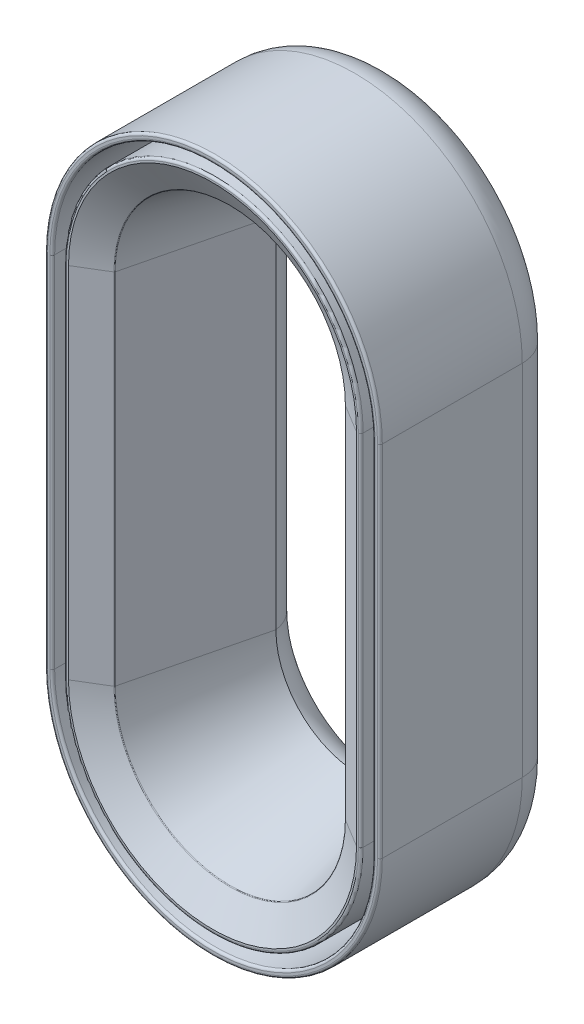
SolidWorks part; units mm, degrees
ref_plane "Ön Düzlem" through (0, 0, 0) normal (0, 0, 1) x (1, 0, 0)
ref_plane "Üst Düzlem" through (0, 0, 0) normal (0, 1, 0) x (1, 0, 0)
ref_plane "Sağ Düzlem" through (0, 0, 0) normal (1, 0, 0) x (0, 0, -1)
sketch "Çizim1" plane through (0, 0, 0) normal (0, 0, 1) x (1, 0, 0)
  line L0 (0, -150) -> (0, 150) construction
  line L1 (-140, -150) -> (-140, 150)
  line L2 (140, -150) -> (140, 150)
  arc A0 (-140, -150) -> (140, -150) centre (0, -150) ccw
  arc A1 (140, 150) -> (-140, 150) centre (0, 150) ccw
  point P2 (0, 0)
  dimension "D1" = 140
  dimension "D2" = 300
extrude "Yükseklik-Ekstrüzyon1" add sketch "Çizim1" along normal blind 150
sketch "Çizim2" plane through (0, 0, 150) normal (0, 0, 1) x (1, 0, 0)
  line L0 (0, -150) -> (0, 150) construction
  line L1 (-70, -150) -> (-70, 150)
  line L2 (70, -150) -> (70, 150)
  arc A0 (-70, -150) -> (70, -150) centre (0, -150) ccw
  arc A1 (70, 150) -> (-70, 150) centre (0, 150) ccw
  point P2 (0, 0)
  dimension "D2" = 70
  dimension "D1" = 300
extrude "Kes-Ekstrüzyon1" cut sketch "Çizim2" against normal blind 150
chamfer "Pah1" distance 30 distance2 123 4 edges at (-70, 0, 150) (0, -220, 150) (0, 220, 150) (70, 0, 150) first distance on face at (0, 0, 150)
sketch "Çizim3" plane through (0, 0, 150) normal (0, 0, 1) x (1, 0, 0)
  line L0 (140, -150) -> (140, 150) construction
  line L1 (-140, 150) -> (-140, -150) construction
  line L2 (140, -150) -> (140, 150)
  line L3 (-140, 150) -> (-140, -150)
  line L4 (-134, 150) -> (-134, -150)
  line L5 (134, -150) -> (134, 150)
  line L6 (-124, 150) -> (-124, -150)
  line L7 (124, -150) -> (124, 150)
  arc A0 (-140, -150) -> (140, -150) centre (0, -150) ccw construction
  arc A1 (140, 150) -> (-140, 150) centre (0, 150) ccw construction
  arc A2 (-140, -150) -> (140, -150) centre (0, -150) ccw
  arc A3 (140, 150) -> (-140, 150) centre (0, 150) ccw
  arc A4 (134, 150) -> (-134, 150) centre (0, 150) ccw
  arc A5 (-134, -150) -> (134, -150) centre (0, -150) ccw
  arc A6 (124, 150) -> (-124, 150) centre (0, 150) ccw
  arc A7 (-124, -150) -> (124, -150) centre (0, -150) ccw
  dimension "D1" = 6
  dimension "D2" = 10
extrude "Kes-Ekstrüzyon2" cut sketch "Çizim3" against normal blind 76 contours L4 A5 L5 A4 A7 L6 A6 L7 region at (0, 277.7195, 150)
sketch "Çizim4" plane through (0, 0, 0) normal (0, 1, 0) x (1, 0, 0)
  line L0 (0, 0) -> (0, -150)
  line L1 (-140, -150) -> (140, -150) construction
  circle A0 centre (0, -75) radius 3.7566
extrude "Kes-Ekstrüzyon3" cut sketch "Çizim4" against normal blind 10 from offset 287 contours L0 A0 | L0 A0 region at (1.5944, 0, 75) region at (-1.5944, 0, 75) offset against normal yes
fillet "Radyus1" radius 31 8 edges at (0, -220, 0) (-70, 0, 0) (0, 220, 0) (0, 290, 0) (140, 0, 0) (0, -290, 0) (70, 0, 0) (-140, 0, 0)
fillet "Radyus2" radius 2 12 edges at (-140, 0, 150) (0, 290, 150) (140, 0, 150) (0, -290, 150) (0, -284, 150) (134, 0, 150) (0, 284, 150) (-134, 0, 150) (0, 274, 150) (124, 0, 150) (0, -274, 150) (-124, 0, 150)
chamfer "Pah2" distance 15 angle 45 4 edges at (100, 0, 150) (0, -250, 150) (0, 250, 150) (-100, 0, 150) first distance on face at (85, 0, 88.5) first distance on face at (0, -192.5, 88.5) first distance on face at (0, 192.5, 88.5) first distance on face at (-85, 0, 88.5)
fillet "Radyus3" radius 1 4 edges at (-96.4457, 0, 135.4272) (0, 246.4457, 135.4272) (96.4457, 0, 135.4272) (0, -246.4457, 135.4272)
